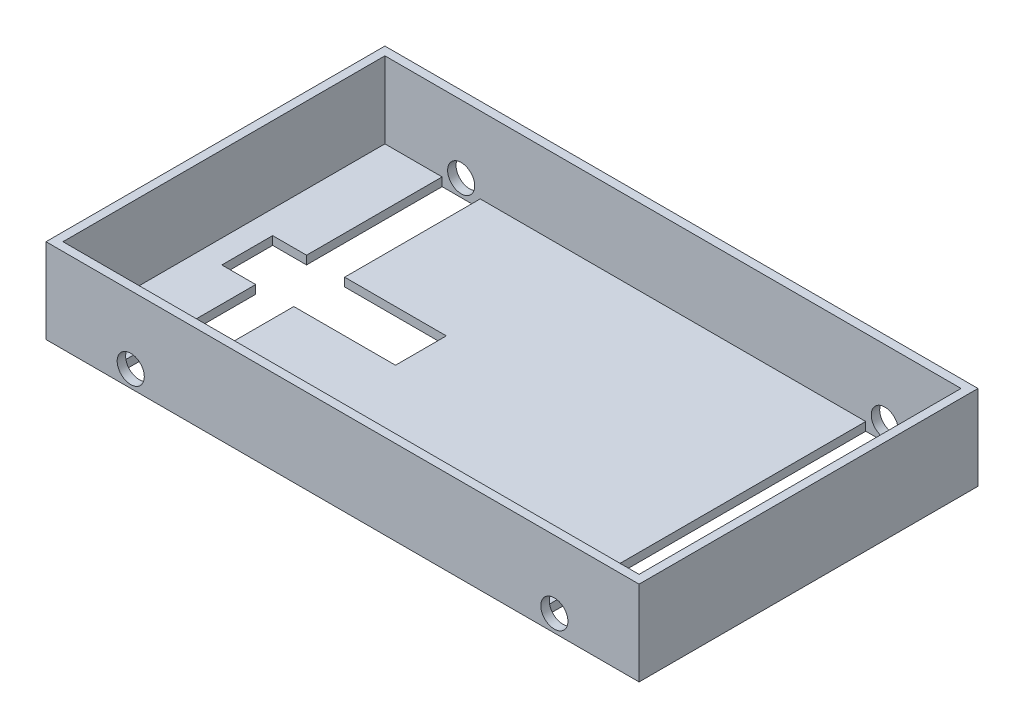
SolidWorks part; units mm, degrees
ref_plane "Front Plane" through (0, 0, 0) normal (0, 0, 1) x (1, 0, 0)
ref_plane "Top Plane" through (0, 0, 0) normal (0, 1, 0) x (1, 0, 0)
ref_plane "Right Plane" through (0, 0, 0) normal (1, 0, 0) x (0, 0, -1)
sketch "Sketch1" plane through (0, 0, 0) normal (0, 1, 0) x (1, 0, 0)
  line L1 (175, -100) -> (-175, -100)
  line L2 (175, -100) -> (175, 100)
  line L3 (175, 100) -> (-175, 100)
  line L4 (-175, -100) -> (-175, 100)
  line L5 (175, -100) -> (-175, 100) construction
  line L6 (175, 100) -> (-175, -100) construction
  point P0 (0, 0)
  dimension "D1" = 200
  dimension "D2" = 350
extrude "Boss-Extrude1" add sketch "Sketch1" along normal blind 50 contours L1 L4 L3 L2
shell "Shell1" thickness 5 removed face at (0, 50, 0)
sketch "Sketch3" plane through (0, 0, 100) normal (0, 0, 1) x (1, 0, 0)
  line L0 (0, -27.5) -> (0, 27.5) construction
  circle A0 centre (-125, 10) radius 8
  circle A1 centre (125, 10) radius 8
  dimension "D1" = 16
  dimension "D2" = 10
  dimension "D3" = 125
extrude "Cut-Extrude1" cut sketch "Sketch3" against normal up to surface (200 mm away) up to face at (0, 25, -100)
sketch "Sketch4" plane through (0, 5, 0) normal (0, 1, 0) x (1, 0, 0)
  line L0 (-136.245, 95) -> (-136.245, -95)
  line L1 (-170, 95) -> (170, 95)
  line L2 (-170, 95) -> (-170, -95)
  line L3 (-170, -95) -> (170, -95)
  line L4 (170, 95) -> (170, -95)
  line L5 (-131.245, 95) -> (-131.245, -95) construction
  line L6 (-113.755, 95) -> (-113.755, -95)
  line L7 (-118.755, -95) -> (-118.755, 95) construction
  line L8 (0, -27.5) -> (0, 27.5) construction
  line L9 (113.755, 95) -> (113.755, -95)
  line L10 (136.245, 95) -> (136.245, -95)
  line M2 (-118.755, 95) -> (-118.755, -95)
  line M3 (-118.755, -95) -> (118.755, -95)
  line M4 (118.755, -95) -> (118.755, 95)
  line M5 (118.755, 95) -> (-118.755, 95)
  dimension "D1" = 5
  dimension "D2" = 5
extrude "Cut-Extrude4" cut sketch "Sketch4" against normal blind 10 contours L0 L3 L1 M2 | L6 L1 M2 M3 | L9 M5 M3 M4 | L10 L1 L3 M4 region at (-127.5, 5, 0) region at (-116.255, 5, 0) region at (116.255, 5, 0) region at (127.5, 5, 0)
sketch "Sketch5" plane through (0, 5, 0) normal (0, 1, 0) x (1, 0, 0)
  line L5 (-136.245, 95) -> (-136.245, -95) construction
  line L6 (-156.245, 15) -> (-53.755, 15)
  line L7 (-156.245, 15) -> (-156.245, -15)
  line L8 (-156.245, -15) -> (-53.755, -15)
  line L9 (-53.755, 15) -> (-53.755, -15)
  line L11 (-113.755, 95) -> (-113.755, -95) construction
  point P4 (-53.755, 0)
  point P9 (-136.245, 0)
  dimension "D1" = 60
  dimension "D2" = 20
  dimension "D3" = 30
extrude "Cut-Extrude5" cut sketch "Sketch5" against normal blind 10
